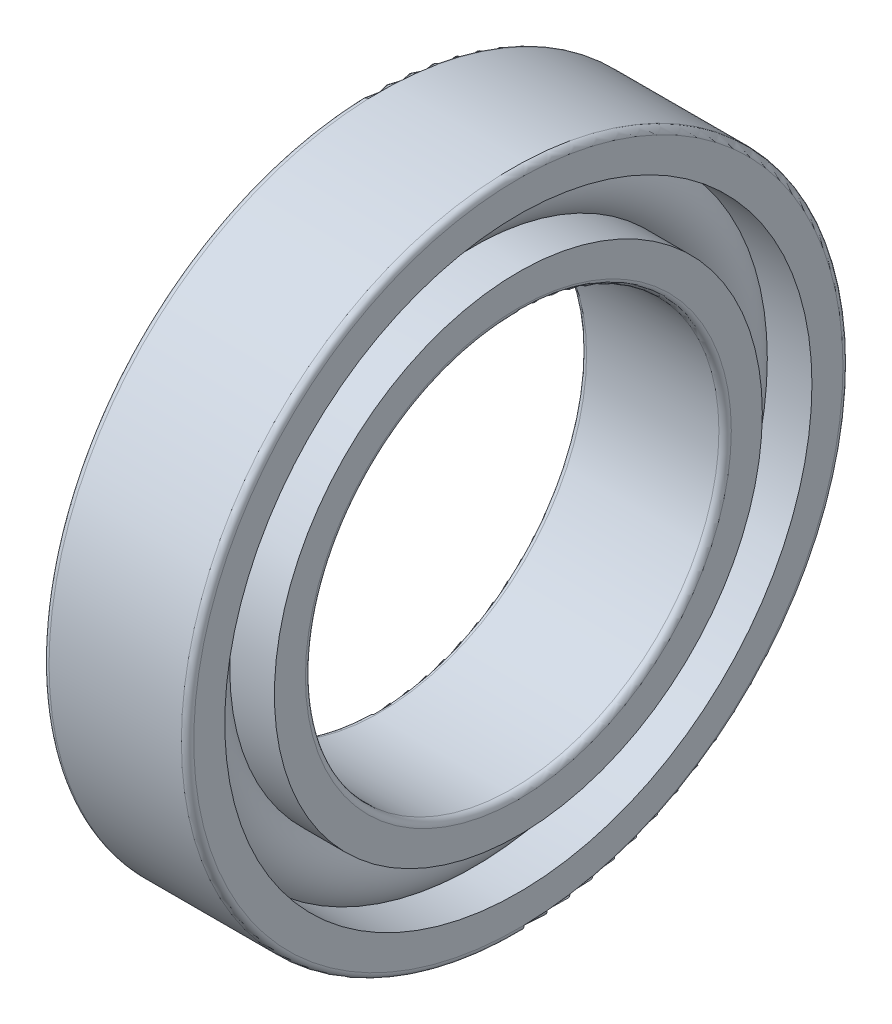
SolidWorks part; units mm, degrees
ref_plane "Plane1" through (0, 0, 0) normal (0, 0, 1) x (1, 0, 0)
ref_plane "Plane2" through (0, 0, 0) normal (0, 1, 0) x (1, 0, 0)
ref_plane "Plane3" through (0, 0, 0) normal (1, 0, 0) x (0, 0, -1)
sketch "Clipboard" plane through (0, 0, 0) normal (0, 0, 1) x (1, 0, 0)
  line L0 (-10, 0) -> (10, 0) construction
  line L1 (0, 0) -> (22.3471, -0.7804)
  line L2 (0, 0) -> (12.9921, 0.4537)
  line L3 (0, 0) -> (22.3471, -0.7804)
  line L4 (0, 0) -> (-22.3573, -0.3902)
  dimension "BallCLRad" = 13
sketch "CagSpiSke" plane through (0, 0, 0) normal (0, 0, 1) x (1, 0, 0)
  line L0 (0.18, 12.7) -> (0.18, 13.3)
  line L1 (0.18, 13.3) -> (-0.18, 13.3)
  line L2 (-0.18, 13.3) -> (-0.18, 12.7)
  line L3 (-0.18, 12.7) -> (0.18, 12.7)
  line L4 (-20.6375, 0) -> (20.6375, 0) construction
  line L5 (0, 0) -> (0, 23.7692) construction
  dimension "OD" = 26.6
  dimension "ID" = 25.4
revolve "CageSpine" add sketch "CagSpiSke" angle 0.001 about L4 reverse direction yes
ref_axis "Axis1" through (-50, 0, 0) along (1, 0, 0)
sketch "CagBalSke" plane through (0, 0, 0) normal (0, 0, 1) x (1, 0, 0)
  line L0 (-1.98, 13) -> (1.98, 13)
  line L1 (-1.905, 13) -> (1.905, 13) construction
  line L2 (-10, 0) -> (10, 0) construction
  line L3 (0, 0) -> (0, 24) construction
  arc A0 (1.98, 13) -> (-1.98, 13) centre (0, 13) cw
  dimension "BallCLRad" = 13
revolve "CageBall" [suppressed] add sketch "CagBalSke" angle 360 about L1 reverse direction yes
pattern_circular "CageBalls" [suppressed] count 2 every 180 about axis through (-50, 0, 0) along (1, 0, 0)
sketch "CagTrmODSke" plane through (0, 0, 0) normal (0, 0, 1) x (1, 0, 0)
  line L0 (1.981, 13.3) -> (1.981, 14.981)
  line L1 (1.981, 14.981) -> (-1.981, 14.981)
  line L2 (-1.981, 14.981) -> (-1.981, 13.3)
  line L3 (-1.981, 13.3) -> (1.981, 13.3)
  line L4 (-20.6375, 0) -> (20.6375, 0) construction
  line L5 (0, 0) -> (0, 25) construction
  dimension "Width" = 3.962
  dimension "ID" = 26.6
  dimension "OD" = 29.962
revolve "CageTrimOD" [suppressed] cut sketch "CagTrmODSke" angle 360 about L4 reverse direction yes
sketch "CagTrmIDSke" plane through (0, 0, 0) normal (0, 0, 1) x (1, 0, 0)
  line L0 (1.981, 11.021) -> (1.981, 12.7)
  line L1 (1.981, 12.7) -> (-1.981, 12.7)
  line L2 (-1.981, 12.7) -> (-1.981, 11.021)
  line L3 (-1.981, 11.021) -> (1.981, 11.021)
  line L4 (-20.6375, 0) -> (20.6375, 0) construction
  line L5 (0, 0) -> (0, 25) construction
  dimension "Width" = 3.962
  dimension "ID" = 22.042
  dimension "OD" = 25.4
revolve "CageTrimID" [suppressed] cut sketch "CagTrmIDSke" angle 360 about L4 reverse direction yes
sketch "BalSimSke" plane through (0, 0, 0) normal (0, 0, 1) x (1, 0, 0)
  line L0 (-10, 0) -> (10, 0) construction
  line L1 (-10, 13) -> (10, 13) construction
  line L2 (0, 0) -> (0, 23) construction
  circle A0 centre (0, 13) radius 1.8
  dimension "BallCLRad" = 13
  dimension "Ball_diameter" = 3.6
revolve "BallsSimplified" add sketch "BalSimSke" angle 360 about L0
sketch "BalDetSke" plane through (0, 0, 0) normal (0, 0, 1) x (1, 0, 0)
  line L0 (-1.8, 13) -> (1.8, 13)
  line L1 (-1.905, 13) -> (1.905, 13) construction
  line L2 (0, 0) -> (0, 25) construction
  arc A0 (1.8, 13) -> (-1.8, 13) centre (0, 13) cw
  dimension "BallCLRad" = 13
  dimension "Ball_diameter" = 3.6
revolve "BallDetailed" [suppressed] add sketch "BalDetSke" angle 360 about L1 reverse direction yes
sketch "InnRacSke" plane through (0, 0, 0) normal (0, 0, 1) x (1, 0, 0)
  line L0 (-1.3079, 11.8) -> (-3.5, 11.8)
  line L1 (-3.5, 11.8) -> (-3.5, 10.3)
  line L2 (-3.2, 10) -> (3.2, 10)
  line L3 (3.5, 10.3) -> (3.5, 11.8)
  line L4 (3.5, 11.8) -> (1.3079, 11.8)
  line L5 (-20.6375, 0) -> (20.6375, 0) construction
  line L6 (0, 0) -> (0, 30) construction
  arc A0 (-3.5, 10.3) -> (-3.2, 10) centre (-3.2, 10.3) ccw
  arc A1 (3.2, 10) -> (3.5, 10.3) centre (3.2, 10.3) ccw
  arc A2 (1.3079, 11.8) -> (-1.3079, 11.8) centre (0, 13) cw
  dimension "BallCLRad" = 13
  dimension "Fillet_radius" = 0.3
  dimension "Ball_diameter" = 3.55
  dimension "ID" = 20
  dimension "OD" = 23.6
  dimension "Width" = 7
revolve "InnerRace" add sketch "InnRacSke" angle 360 about L5 reverse direction yes
sketch "OutRacSke" plane through (0, 0, 0) normal (0, 0, 1) x (1, 0, 0)
  line L0 (-1.3079, 14.2) -> (-3.5, 14.2)
  line L1 (-3.5, 14.2) -> (-3.5, 15.7)
  line L2 (-3.2, 16) -> (3.2, 16)
  line L3 (3.5, 15.7) -> (3.5, 14.2)
  line L4 (3.5, 14.2) -> (1.3079, 14.2)
  line L5 (-20.6375, 0) -> (20.6375, 0) construction
  line L6 (0, 0) -> (0, 30) construction
  arc A0 (-3.5, 15.7) -> (-3.2, 16) centre (-3.2, 15.7) cw
  arc A1 (3.2, 16) -> (3.5, 15.7) centre (3.2, 15.7) cw
  arc A2 (1.3079, 14.2) -> (-1.3079, 14.2) centre (0, 13) ccw
  dimension "BallCLRad" = 13
  dimension "Fillet_radius" = 0.3
  dimension "Ball_diameter" = 3.55
  dimension "Width" = 7
revolve "OuterRace" add sketch "OutRacSke" angle 360 about L5 reverse direction yes
pattern_circular "BallsDetailed" [suppressed] count 2 every 180 about axis through (-50, 0, 0) along (1, 0, 0)
equation "\"BallCLRad@Clipboard\" = ( \"OD@OutRacSke\" + \"ID@InnRacSke\" ) / 4"
equation "\"BallCLRad@BalSimSke\" = \"BallCLRad@Clipboard\""
equation "\"BallCLRad@BalDetSke\" = \"BallCLRad@Clipboard\""
equation "\"BallCLRad@InnRacSke\" = \"BallCLRad@Clipboard\""
equation "\"BallCLRad@OutRacSke\" = \"BallCLRad@Clipboard\""
equation "\"Ball_diameter@InnRacSke\" = \"Ball_diameter@BalDetSke\" - 0.05"
equation "\"Ball_diameter@OutRacSke\" = \"Ball_diameter@BalDetSke\" - 0.05"
equation "\"Ball_diameter@BalSimSke\" = \"Ball_diameter@BalDetSke\""
equation "\"Width@OutRacSke\" = \"Width@InnRacSke\""
equation "\"Fillet_radius@OutRacSke\" = \"Fillet_radius@InnRacSke\""
equation "\"Max_count@Clipboard\" = int( 3.14159265 / atn(( \"Ball_diameter@BalDetSke\" / 2) / sqr( \"BallCLRad@Clipboard\"  *  \"BallCLRad@Clipboard\" - ( \"Ball_diameter@BalDetSke\" / 2) *  ( \"Ball_diameter@BalDetSke\" / 2))))"
equation "\"Max_count@Clipboard\" = ((sgn( \"Max_count@Clipboard\" - \"Count@Clipboard\" )-1)*( \"Max_count@Clipboard\" - \"Count@Clipboard\" ))/-2+ \"Count@Clipboard\""
equation "\"Count@BallsDetailed\" = int( \"Show_count@Clipboard\" ) "
equation "\"Count@BallsDetailed\" = ((sgn( \"Count@BallsDetailed\" - \"Max_count@Clipboard\" )-1)*( \"Count@BallsDetailed\" - \"Max_count@Clipboard\" ))/-2+ \"Max_count@Clipboard\""
equation "\"Count@BallsDetailed\" = ((sgn( \"Count@BallsDetailed\" - \"Min_count@Clipboard\" )+1)*( \"Count@BallsDetailed\" - \"Min_count@Clipboard\"))/2 +\"Min_count@Clipboard\""
equation "\"Angle@BallsDetailed\" = 360.0 / \"Max_count@Clipboard\""
equation "\"BallCLRad@CagBalSke\" = \"BallCLRad@Clipboard\""
equation "\"Count@CageBalls\" = \"Count@BallsDetailed\""
equation "\"Angle@CageBalls\" = \"Angle@BallsDetailed\""
equation "\"Angle@CageSpine\" =  \"Angle@CageBalls\" * ( \"Count@CageBalls\" -1 + int( \"Count@CageBalls\" / \"Max_count@Clipboard\" ) )  + 0.001 -  int( \"Count@CageBalls\" / \"Max_count@Clipboard\" ) * 0.001"
equation "\"Angle@CageSpine\" =  \"Angle@CageSpine\" * int( \"Min_count@Clipboard\" / 2) + int(1 / \"Min_count@Clipboard\")  * 0.001"
equation "\"CageWallOD@CagBalSke\" =  \"Ball_diameter@BalDetSke\" * 1.1"
equation "\"Thickness@CagSpiSke\" =  \"Ball_diameter@BalDetSke\" * 0.1"
equation "\"OD@CagTrmODSke\" = \"BallCLRad@Clipboard\" * 2 + \"CageWallOD@CagBalSke\" + 0.002"
equation "\"ID@CagTrmODSke\" = \"BallCLRad@Clipboard\" * 2 + \"Ball_diameter@BalDetSke\" / 6"
equation "\"OD@CagTrmIDSke\" = \"BallCLRad@Clipboard\" * 2 - \"Ball_diameter@BalDetSke\" / 6"
equation "\"ID@CagTrmIDSke\" = \"BallCLRad@Clipboard\" * 2 - \"CageWallOD@CagBalSke\" + 0.002"
equation "\"OD@CagSpiSke\" = \"ID@CagTrmODSke\""
equation "\"ID@CagSpiSke\" = \"OD@CagTrmIDSke\""
equation "\"Width@CagTrmODSke\" = \"CageWallOD@CagBalSke\" + 0.002"
equation "\"Width@CagTrmIDSke\" = \"CageWallOD@CagBalSke\" + 0.002"
